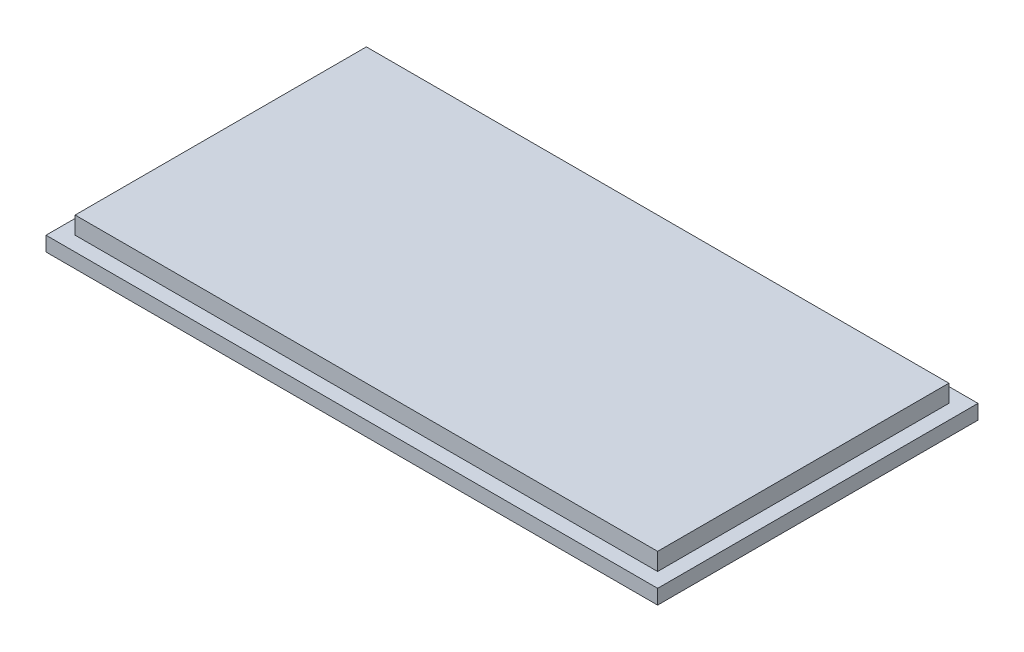
SolidWorks part; units mm, degrees
ref_plane "Front Plane" through (0, 0, 0) normal (0, 0, 1) x (1, 0, 0)
ref_plane "Top Plane" through (0, 0, 0) normal (0, 1, 0) x (1, 0, 0)
ref_plane "Right Plane" through (0, 0, 0) normal (1, 0, 0) x (0, 0, -1)
sketch "Sketch1" plane through (0, 0, 0) normal (0, 1, 0) x (1, 0, 0)
  line L1 (-105, 55) -> (105, 55)
  line L2 (-105, 55) -> (-105, -55)
  line L3 (-105, -55) -> (105, -55)
  line L4 (105, 55) -> (105, -55)
  point P6 (-70.6658, -46.435)
  point P7 (-87.7956, 58.3742)
  point P9 (-85.0906, -51.6258)
  dimension "D1" = 110
  dimension "D2" = 210
  dimension "D3" = 105
  dimension "D4" = 55
extrude "Boss-Extrude1" add sketch "Sketch1" along normal blind 5
sketch "Sketch2" plane through (0, 5, 0) normal (0, 1, 0) x (1, 0, 0)
  line L1 (-100, -50) -> (100, -50)
  line L2 (-100, -50) -> (-100, 50)
  line L3 (-100, 50) -> (100, 50)
  line L4 (100, -50) -> (100, 50)
  dimension "D1" = 100
  dimension "D2" = 200
  dimension "D3" = 100
  dimension "D4" = 50
extrude "Boss-Extrude2" add sketch "Sketch2" along normal blind 6
